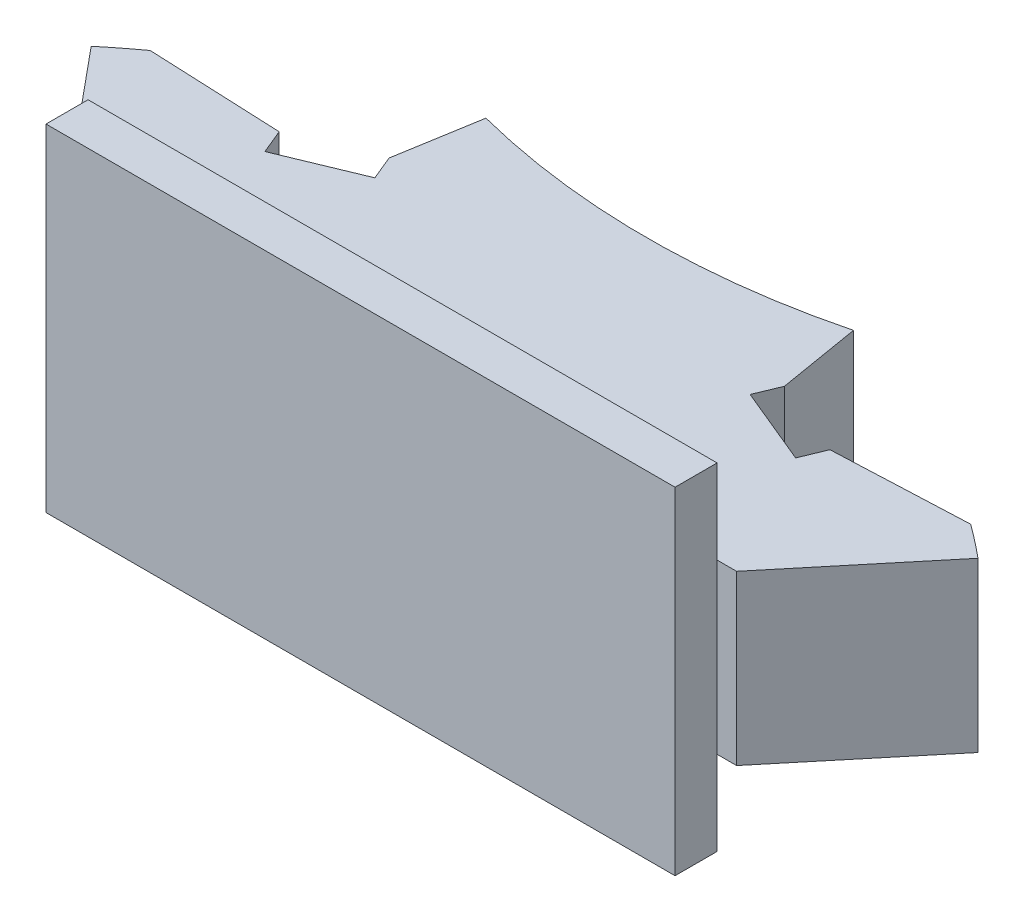
SolidWorks part; units mm, degrees
ref_plane "Front Plane" through (0, 0, 0) normal (0, 0, 1) x (1, 0, 0)
ref_plane "Top Plane" through (0, 0, 0) normal (0, 1, 0) x (1, 0, 0)
ref_plane "Right Plane" through (0, 0, 0) normal (1, 0, 0) x (0, 0, -1)
sketch "Sketch1" plane through (0, 0, 0) normal (0, 1, 0) x (1, 0, 0)
  line L0 (0, 0) -> (0, 52.451)
  line L1 (0, 0) -> (20.0721, 48.4584)
  line L2 (0, 0) -> (-20.0721, 48.4584)
  line L3 (14.9214, 44.3201) -> (20.788, 41.89)
  line L4 (-20.788, 41.89) -> (-14.9214, 44.3201)
  line L5 (-14.9214, 44.3201) -> (-13.8733, 50.583)
  line L6 (-20.788, 41.89) -> (-30.9662, 42.3344)
  line L7 (14.9214, 44.3201) -> (13.8733, 50.583)
  line L8 (20.788, 41.89) -> (30.9662, 42.3344)
  line L9 (-20.788, 41.89) -> (-14.9214, 44.3201)
  line L10 (-20.788, 41.89) -> (-20.0298, 40.0596)
  line L11 (-14.9214, 44.3201) -> (-14.1632, 42.4897)
  line L12 (-20.0298, 40.0596) -> (-14.1632, 42.4897)
  line L13 (14.9214, 44.3201) -> (20.788, 41.89)
  line L14 (14.9214, 44.3201) -> (14.1632, 42.4897)
  line L15 (20.788, 41.89) -> (20.0298, 40.0596)
  line L16 (14.1632, 42.4897) -> (20.0298, 40.0596)
  line L17 (-42.7297, 30.4184) -> (42.7297, 30.4184)
  line L18 (0, 0) -> (22.5802, 27.2434)
  line L19 (0, 0) -> (-22.5802, 27.2434)
  line L20 (-44.8208, 27.2434) -> (-23.7417, 27.2434)
  line L21 (-23.7417, 30.4184) -> (-23.7417, 27.2434)
  line L22 (23.7417, 30.4184) -> (23.7417, 27.2434)
  line L23 (-23.7417, 28.6448) -> (-33.4709, 40.3832)
  line L24 (-23.7417, 30.4184) -> (23.7417, 30.4184)
  line L25 (22.5802, 27.2434) -> (44.8208, 27.2434)
  line L26 (23.7417, 28.6448) -> (33.4709, 40.3832)
  line L27 (-23.7417, 27.2434) -> (23.7417, 27.2434)
  circle A0 centre (0, 0) radius 52.451
  arc A1 (-13.8733, 50.583) -> (13.8733, 50.583) centre (0, 104.7134) ccw
  point P29 (0, 48.8334)
  point P34 (-17.5972, 42.4834)
  dimension "D1" = 104.902
  dimension "D20" = 55.88
  dimension "D23" = 47.4835
  dimension "D2" = 22.5
  dimension "D3" = 22.5
  dimension "D4" = 32
  dimension "D5" = 6.35
  dimension "D6" = 3.175
  dimension "D7" = 3.175
  dimension "D8" = 3.175
  dimension "D9" = 65
  dimension "D10" = 6.35
  dimension "D11" = 6.35
  dimension "D12" = 65
  dimension "D13" = 32
  dimension "D14" = 1.9812
  dimension "D15" = 1.9812
  dimension "D16" = 18.415
  dimension "D17" = 3.175
  dimension "D18" = 3.175
  dimension "D19" = 3.175
  dimension "D21" = 12.065
  dimension "D22" = 17.5972
  dimension "D24" = 23.7417
extrude "Boss-Extrude1" add sketch "Sketch1" against normal blind 12.7 contours L0 A0 L5 L11 L12 L2 L17 | L7 A0 L0 L17 L1 L16 L14 | L18 A0 L8 L15 L16 L1 L17 | L6 A0 L19 L17 L2 L12 L10 region at (-7.5267, 0, -40.0318) region at (7.5267, 0, -40.0318) region at (22.6731, 0, -36.3485) region at (-22.6731, 0, -36.3485)
extrude "Boss-Extrude2" add sketch "Sketch1<5>" along normal blind 6.35 separate body contours L17 L21 L20 L2 | L2 L20 L0 L17 | L0 L20 L1 L17 | L22 L17 L1 L20 region at (-5.9771, 0, -28.8601) region at (5.9771, 0, -28.8601) region at (17.8358, 0, -28.8014) region at (-17.8358, 0, -28.8014)
sketch "Sketch1<5>" plane through (0, 0, 0) normal (0, 1, 0) x (1, 0, 0) same geometry as "Sketch1"
extrude "Boss-Extrude3" add sketch "Sketch1<6>" against normal blind 19.05 contours L17 L21 L20 L2 | L2 L20 L0 L17 | L0 L20 L1 L17 | L22 L17 L1 L20 region at (-5.9771, 0, -28.8601) region at (5.9771, 0, -28.8601) region at (17.8358, 0, -28.8014) region at (-17.8358, 0, -28.8014)
sketch "Sketch1<6>" plane through (0, 0, 0) normal (0, 1, 0) x (1, 0, 0) same geometry as "Sketch1"
